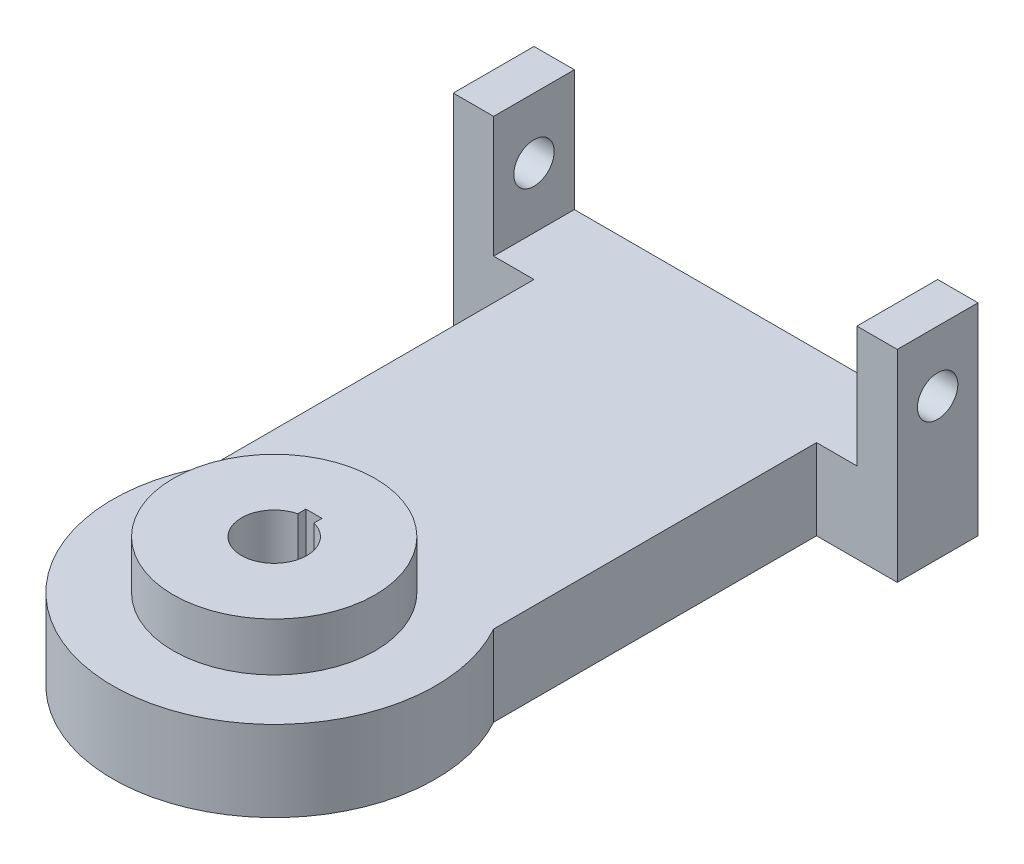
SolidWorks part; units mm, degrees
ref_plane "Front Plane" through (0, 0, 0) normal (0, 0, 1) x (1, 0, 0)
ref_plane "Top Plane" through (0, 0, 0) normal (0, 1, 0) x (1, 0, 0)
ref_plane "Right Plane" through (0, 0, 0) normal (1, 0, 0) x (0, 0, -1)
sketch "Sketch1" plane through (0, 0, 0) normal (0, 1, 0) x (1, 0, 0)
  circle A21 centre (0, 0) radius 20
  dimension "D1" = 40
extrude "Boss-Extrude1" add sketch "Sketch1" along normal blind 10
sketch "Sketch2" plane through (0, 10, 0) normal (0, 1, 0) x (1, 0, 0)
  line L0 (-1, 3.9246) -> (-1, 4.9246)
  line L1 (-1, 4.9246) -> (1, 4.9246)
  line L2 (1, 4.9246) -> (1, 3.9246)
  arc A1 (-1, 3.9246) -> (1, 3.9246) centre (0, 0) ccw
  point P4 (0, 4.9246)
  dimension "D1" = 8.1
  dimension "D2" = 1
  dimension "D3" = 2
extrude "Cut-Extrude1" cut sketch "Sketch2" against normal through all
sketch "Sketch3" plane through (0, 0, 0) normal (0, 1, 0) x (1, 0, 0)
  line L0 (-17.5, 59.6825) -> (-17.5, 9.6825)
  line L1 (-17.5, 59.6825) -> (17.5, 59.6825)
  line L2 (17.5, 59.6825) -> (17.5, 9.6825)
  circle A0 centre (0, 0) radius 20 construction
  arc A1 (17.5, 9.6825) -> (-17.5, 9.6825) centre (0, 0) ccw
  point P6 (0, 59.6825)
  point P9 (0, 20)
  dimension "D1" = 35
  dimension "D2" = 50
extrude "Boss-Extrude2" add sketch "Sketch3" along normal up to surface (10 mm away) up to face at (0, 10, -2.431)
sketch "Sketch6" plane through (0, 10, 0) normal (0, 1, 0) x (1, 0, 0)
  line L0 (-1, 4.9246) -> (1, 4.9246)
  line L1 (1, 4.9246) -> (1, 3.9246)
  line L2 (1, 3.9246) -> (1, 4.9246) construction
  line L3 (-1, 4.9246) -> (-1, 3.9246)
  line L4 (-1, 4.9246) -> (-1, 3.9246) construction
  circle A0 centre (0, 0) radius 12.5
  arc A1 (-1, 3.9246) -> (1, 3.9246) centre (0, 0) ccw
  arc A2 (-1, 3.9246) -> (1, 3.9246) centre (0, 0) ccw construction
  dimension "D1" = 25
extrude "Boss-Extrude3" add sketch "Sketch6" along normal blind 6
sketch "Sketch7" plane through (0, 0, -59.6825) normal (0, 0, -1) x (-1, 0, 0)
  line L0 (-27.5, 0) -> (-27.5, 25)
  line L1 (-27.5, 25) -> (-22.5, 25)
  line L2 (-22.5, 25) -> (-22.5, 10)
  line L3 (-17.5, 10) -> (17.5, 10) construction
  line L4 (-22.5, 10) -> (22.5, 10)
  line L5 (22.5, 10) -> (22.5, 25)
  line L6 (22.5, 25) -> (27.5, 25)
  line L7 (27.5, 25) -> (27.5, 0)
  line L8 (27.5, 0) -> (-27.5, 0)
  dimension "D1" = 5
  dimension "D2" = 15
  dimension "D3" = 45
extrude "Boss-Extrude4" add sketch "Sketch7" against normal blind 10
sketch "Sketch8" plane through (-27.5, 0, 0) normal (-1, 0, 0) x (0, 0, 1)
  line L1 (-49.6825, 25) -> (-59.6825, 25) construction
  circle A0 centre (-54.6825, 17.5) radius 2.5
  point P2 (0, 0)
  point P7 (-54.6825, 25)
  dimension "D2" = 5
  dimension "D1" = 7.5
extrude "Cut-Extrude2" cut sketch "Sketch8" against normal through all
